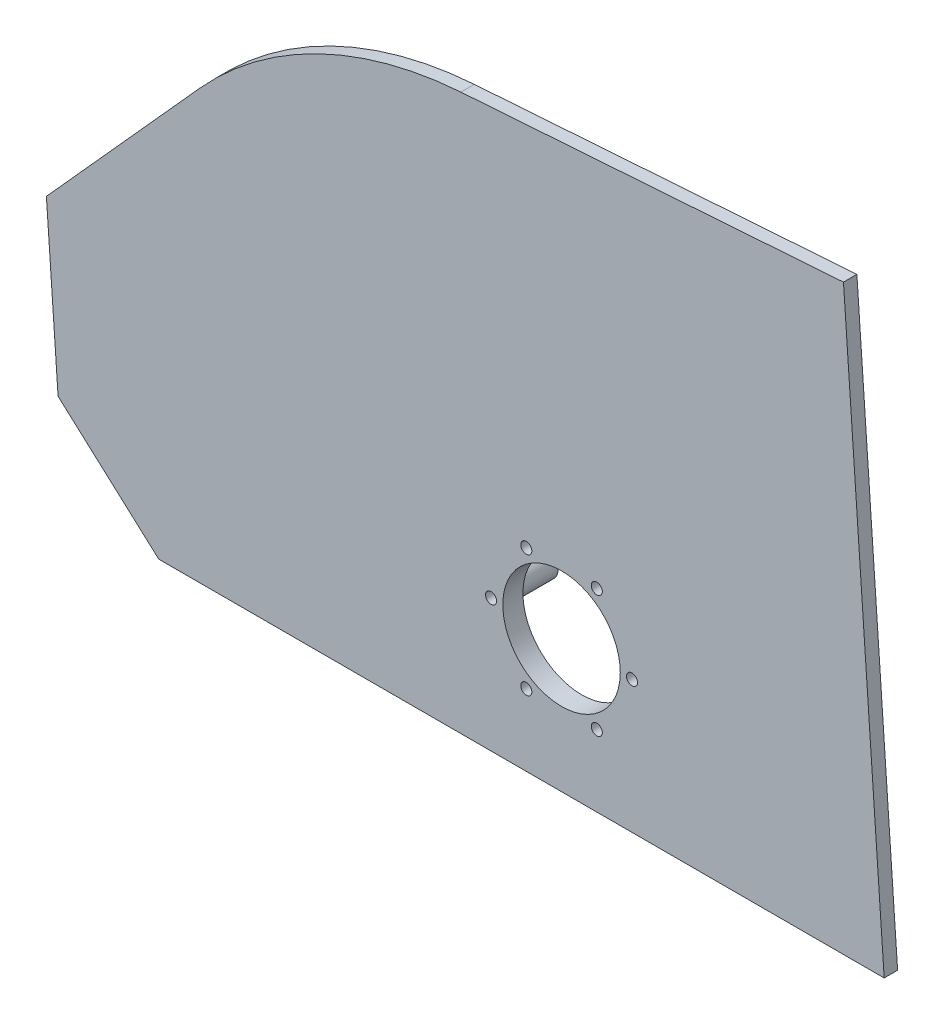
SolidWorks part; units mm, degrees
material "ABS"
ref_plane "Front Plane" through (0, 0, 0) normal (0, 0, 1) x (1, 0, 0)
ref_plane "Top Plane" through (0, 0, 0) normal (0, 1, 0) x (1, 0, 0)
ref_plane "Right Plane" through (0, 0, 0) normal (1, 0, 0) x (0, 0, -1)
sketch "Sketch2" plane through (0, 0, 0) normal (0, 0, 1) x (1, 0, 0)
  line L0 (-153.4878, 37.3903) -> (-150, -12.4879)
  line L1 (-150, -12.4879) -> (-120, -39.5)
  line L2 (-120, -39.5) -> (96.1323, -39.5)
  line L3 (-30, 126.0283) -> (84, 134)
  line L5 (-153.4878, 37.3903) -> (-107.8787, 88.0443)
  line L7 (96.1323, -39.5) -> (84, 134)
  line L8 (0, 0) -> (54, 54) construction
  line L11 (-47.6182, 0) -> (49.7288, 0) construction
  line L12 (-42.5, 13.2583) -> (-42.5, -13.2583)
  line L17 (-37.5, 13.2583) -> (-37.5, -13.2583)
  line L18 (-42.5, 13.2583) -> (-37.5, 13.2583) construction
  line L19 (0, -75.7784) -> (0, 71.0771) construction
  line L20 (42.5, 13.2583) -> (42.5, -13.2583)
  line L21 (37.5, 13.2583) -> (37.5, -13.2583)
  circle A0 centre (0, 0) radius 34.5 construction
  circle A1 centre (54, 54) radius 4 construction
  circle A8 centre (0, 0) radius 16 construction
  circle A9 centre (0, 0) radius 17.5
  circle A10 centre (0, 0) radius 21 construction
  circle A11 centre (-10.5, 18.1865) radius 1.65
  arc A17 (-107.8787, 88.0443) -> (-30, 126.0283) centre (-21.9325, 10.658) cw
  arc A19 (-14.487, 17.8641) -> (-22.7143, 3.614) centre (0, 0) ccw
  arc A20 (-8.2273, 21.4782) -> (-14.487, 17.8641) centre (-10.5, 18.1865) ccw
  circle A21 centre (10.5, 18.1865) radius 1.65
  arc A22 (14.487, 17.8641) -> (8.2273, 21.4782) centre (10.5, 18.1865) ccw
  circle A23 centre (21, 0) radius 1.65
  arc A24 (22.7143, -3.614) -> (22.7143, 3.614) centre (21, 0) ccw
  circle A25 centre (10.5, -18.1865) radius 1.65
  arc A26 (8.2273, -21.4782) -> (14.487, -17.8641) centre (10.5, -18.1865) ccw
  circle A27 centre (-10.5, -18.1865) radius 1.65
  arc A28 (-14.487, -17.8641) -> (-8.2273, -21.4782) centre (-10.5, -18.1865) ccw
  circle A29 centre (-21, 0) radius 1.65
  arc A30 (-22.7143, 3.614) -> (-22.7143, -3.614) centre (-21, 0) ccw
  arc A31 (8.2273, 21.4782) -> (-8.2273, 21.4782) centre (0, 0) ccw
  arc A32 (22.7143, 3.614) -> (14.487, 17.8641) centre (0, 0) ccw
  arc A33 (14.487, -17.8641) -> (22.7143, -3.614) centre (0, 0) ccw
  arc A34 (-8.2273, -21.4782) -> (8.2273, -21.4782) centre (0, 0) ccw
  arc A35 (-22.7143, -3.614) -> (-14.487, -17.8641) centre (0, 0) ccw
  arc A36 (-37.5, 13.2583) -> (-42.5, 13.2583) centre (-40, 17) ccw
  circle A37 centre (-40, 17) radius 2.2
  circle A38 centre (-40, -17) radius 2.2
  arc A39 (-37.5, -13.2583) -> (-42.5, -13.2583) centre (-40, -17) cw
  circle A40 centre (40, 17) radius 2.2
  arc A41 (37.5, 13.2583) -> (42.5, 13.2583) centre (40, 17) cw
  circle A42 centre (40, -17) radius 2.2
  arc A43 (37.5, -13.2583) -> (42.5, -13.2583) centre (40, -17) ccw
  point P42 (0, 0)
  point P45 (0, 0)
  point P46 (-40, 13.2583)
  point P47 (-37.5, 0)
  point P56 (-42.5, 0)
  dimension "D1" = 69
  dimension "D3" = 6
  dimension "D4" = 5
  dimension "D5" = 54
  dimension "D6" = 45
  dimension "D7" = 8
  dimension "D8" = 80
  dimension "D26" = 32
  dimension "D27" = 1.5
  dimension "D28" = 42
  dimension "D29" = 3.3
  dimension "D9" = 2
  dimension "D10" = 86
  dimension "D11" = 42
  dimension "D12" = 30
  dimension "D13" = 50
  dimension "D14" = 150
  dimension "D15" = 30
  dimension "D16" = 8
  dimension "D17" = 34
  dimension "D18" = 5
  dimension "D19" = 3
  dimension "D20" = 9
  dimension "D21" = 4.4
  dimension "D22" = 35
  dimension "D23" = 30
  dimension "D24" = 249.6201
  dimension "D25" = 80
extrude "Boss-Extrude2" add sketch "Sketch2" against normal blind 4 contours L7 L3 A17 L5 L0 L1 L2 A0 | A1 | A19 A30 A35 A28 A34 A26 A33 A24 A32 A22 A31 A20 | A9 | A39 L12 A36 L17 | A41 L20 A43 L21 region at (-20.3744, 41.3709, 0)
extrude "Boss-Extrude3" add sketch "Sketch2<3>" against normal blind 6 contours A30 A35 A28 A34 A26 A33 A24 A32 A22 A31 A20 A19 A9 A11 A21 A23 A25 A27 A29 | A21 | A25 | A23 | A11 | A27 | A29 region at (-12.1603, 21.0622, 0)
sketch "Sketch2<3>" plane through (0, 0, 0) normal (0, 0, 1) x (1, 0, 0) same geometry as "Sketch2"
extrude "Cut-Extrude1" cut sketch "Sketch2<6>" along direction (0, 0, 1) on the side against the normal through all contours A21 | A23 | A25 | A27 | A29 | A11
sketch "Sketch2<6>" plane through (0, 0, 0) normal (0, 0, 1) x (1, 0, 0) same geometry as "Sketch2"
extrude "Boss-Extrude4" add sketch "Sketch2<7>" against normal blind 34.5 contours L21 A43 L20 A41 | L12 A39 L17 A36
sketch "Sketch2<7>" plane through (0, 0, 0) normal (0, 0, 1) x (1, 0, 0) same geometry as "Sketch2"
extrude "Cut-Extrude2" cut sketch "Sketch2<8>" along normal blind 7 from surface contours A40 | A42 | A37 | A38 starting at face at (40, 0, -34.5)
sketch "Sketch2<8>" plane through (0, 0, 0) normal (0, 0, 1) x (1, 0, 0) same geometry as "Sketch2"
sketch "Sketch3" plane through (0, 0, -4) normal (0, 0, -1) x (-1, 0, 0)
  line L0 (-54, 72.5926) -> (-54, 40.942) construction
  line L1 (-74, 62) -> (-34, 62)
  line L2 (-74, 62) -> (-74, 44)
  line L3 (-74, 44) -> (-34, 44)
  line L4 (-34, 62) -> (-34, 44)
  line L5 (-80.743, 54) -> (-25.619, 54) construction
  circle A0 centre (-54, 54) radius 4 construction
  circle A1 centre (-68, 51) radius 2.2
  circle A2 centre (-40, 51) radius 2.2
  dimension "D1" = 8
  dimension "D6" = 4.4
  dimension "D2" = 40
  dimension "D3" = 8
  dimension "D4" = 10
  dimension "D5" = 20
  dimension "D7" = 3
  dimension "D8" = 28
extrude "Boss-Extrude5" add sketch "Sketch3" along normal blind 3 contours L2 L1 L4 L3
extrude "Cut-Extrude4" cut sketch "Sketch3<4>" against normal blind 6 from surface contours A2 | A1 starting at face at (54, 53, -7)
sketch "Sketch3<4>" plane through (0, 0, -4) normal (0, 0, -1) x (-1, 0, 0) same geometry as "Sketch3"
fillet "Fillet1" radius 1 4 edges at (74, 44, -5.5) (34, 44, -5.5) (34, 62, -5.5) (74, 62, -5.5)
